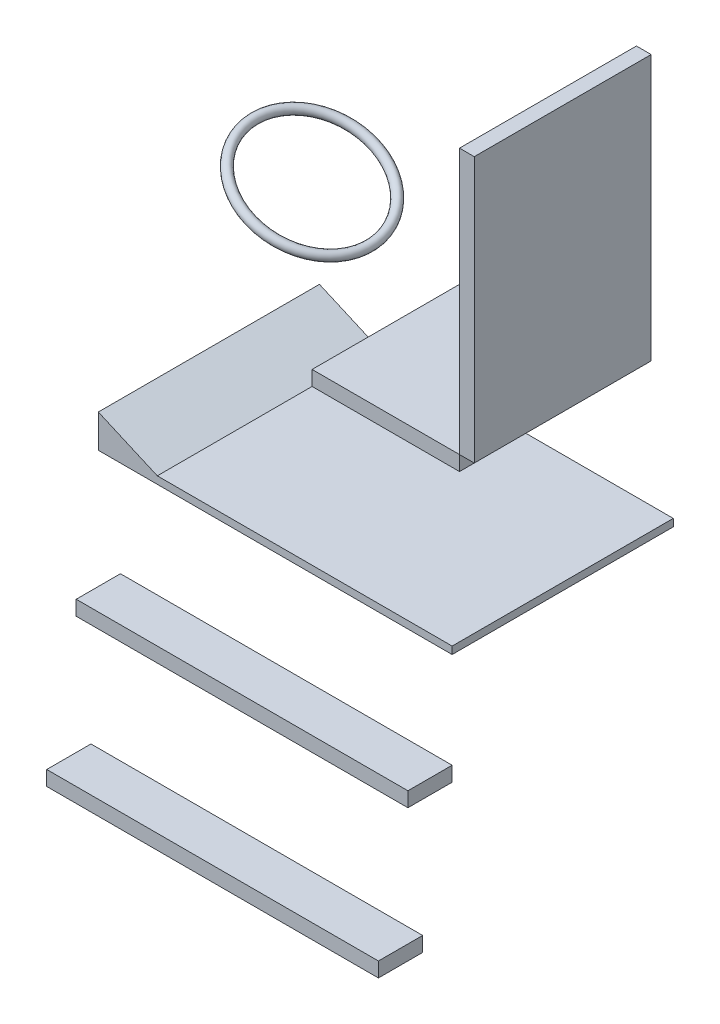
SolidWorks part; units mm, degrees
ref_plane "Right Plane" through (0, 0, 0) normal (0, 0, 1) x (1, 0, 0)
ref_plane "Ground Plane" through (0, 0, 0) normal (0, 1, 0) x (1, 0, 0)
ref_plane "Front Plane" through (0, 0, 0) normal (1, 0, 0) x (0, 0, -1)
ref_plane "Step 1 top 18in" through (0, 457.2, 0) normal (0, 1, 0) x (1, 0, 0)
ref_plane "Step 2 top 18in" through (0, 914.4, 0) normal (0, 1, 0) x (1, 0, 0)
ref_plane "Truck Floor 50in from ground" through (0, 1270, 0) normal (0, 1, 0) x (1, 0, 0)
ref_plane "Seat Bottom" through (0, 1778, 0) normal (0, 1, 0) x (1, 0, 0)
ref_plane "Steering Wheel Center Height" through (0, 2032, 0) normal (0, 1, 0) x (1, 0, 0)
ref_plane "Center Plane" through (0, 0, -381) normal (0, 0, 1) x (1, 0, 0)
sketch "Floor Dimensions" plane through (0, 1270, 0) normal (0, 1, 0) x (1, 0, 0)
  line L5 (0, 762) -> (0, 0)
  line L7 (0, 0) -> (1219.2, 0)
  line L8 (-670.56, 0) -> (670.56, 0) construction
  line L9 (1219.2, 0) -> (1219.2, 762)
  line L10 (1219.2, 762) -> (0, 762)
  point P3 (0, 381)
  dimension "D1" = 1219.2
  dimension "D2" = 762
sketch "Step 2" plane through (0, 914.4, 0) normal (0, 1, 0) x (1, 0, 0)
  line L0 (1219.2, 0) -> (1219.2, 762) construction
  line L1 (76.2, -152.4) -> (1219.2, -152.4)
  line L2 (76.2, -152.4) -> (76.2, 0)
  line L3 (76.2, 0) -> (1219.2, 0)
  line L4 (1219.2, -152.4) -> (1219.2, 0)
  line L5 (0, 0) -> (1219.2, 0) construction
  dimension "D1" = 1143
  dimension "D2" = 152.4
  dimension "D3" = 152.4
sketch "Sketch4" plane through (0, 457.2, 0) normal (0, 1, 0) x (1, 0, 0)
  line L0 (1219.2, -152.4) -> (1219.2, 0) construction
  line L1 (1219.2, -101.6) -> (76.2, -101.6)
  line L2 (1219.2, -101.6) -> (1219.2, -254)
  line L3 (1219.2, -254) -> (76.2, -254)
  line L4 (76.2, -101.6) -> (76.2, -254)
  line L5 (76.2, -152.4) -> (1219.2, -152.4) construction
  dimension "D1" = 152.4
  dimension "D2" = 101.6
extrude "Step-2" add sketch "Step 2" against normal blind 50.8
extrude "Step-1" add sketch "Sketch4" against normal blind 50.8 separate body
sketch "Sketch5" plane through (0, 1778, 0) normal (0, 1, 0) x (1, 0, 0)
  line L0 (660.4, 76.2) -> (660.4, 685.8)
  line L1 (660.4, 76.2) -> (1168.4, 76.2)
  line L2 (660.4, 685.8) -> (1168.4, 685.8)
  line L3 (1168.4, 76.2) -> (1168.4, 685.8)
  line L4 (660.4, 76.2) -> (1168.4, 685.8) construction
  line L5 (660.4, 685.8) -> (1168.4, 76.2) construction
  line L6 (-670.56, 381) -> (670.56, 381) construction
  line L7 (0, 762) -> (0, 0) construction
  point P1 (914.4, 381)
  dimension "D1" = 609.6
  dimension "D2" = 660.4
  dimension "D3" = 508
extrude "Seat-Bottom" add sketch "Sketch5" against normal blind 50.8 separate body
sketch "Sketch6" plane through (0, 0, -381) normal (0, 0, 1) x (1, 0, 0)
  line L0 (1219.2, 1778) -> (1219.2, 2692.4)
  line L7 (1168.4, 1778) -> (1168.4, 2692.4)
  line L8 (1219.2, 2692.4) -> (1168.4, 2692.4)
  line L9 (1168.4, 1778) -> (1219.2, 1778)
  line L10 (558.8, 1778) -> (-558.8, 1778) construction
  dimension "D1" = 914.4
  dimension "D2" = 1219.2
extrude "Seat-Back" add sketch "Sketch6" along normal up to vertex (-304.8 mm away) and the other way up to vertex (-304.8 mm away) separate body up to point (1168.4, 1778, -685.8) other way up to point (1168.4, 1778, -76.2)
sketch "Sketch7" plane through (0, 0, -381) normal (0, 0, 1) x (1, 0, 0)
  line L0 (0, 1358.9) -> (203.2, 1270)
  line L1 (0, -55) -> (0, 55) construction
  line L2 (0, 1270) -> (1219.2, 1270) construction
  line L3 (203.2, 1270) -> (1219.2, 1270)
  line L4 (1219.2, 1270) -> (0, 1270) construction
  line L5 (1219.2, 1270) -> (1219.2, 1244.6)
  line L6 (1219.2, 1244.6) -> (0, 1244.6)
  line L7 (0, 1244.6) -> (0, 1358.9)
  line L8 (660.4, 1727.2) -> (660.4, 1778) construction
  dimension "D1" = 25.4
  dimension "D2" = 457.2
  dimension "D3" = 88.9
extrude "Floor" add sketch "Sketch7" along normal up to vertex (381 mm away) and the other way up to vertex (381 mm away) separate body up to point (1219.2, 1270, 0) other way up to point (1219.2, 1270, -762)
sketch "Steering-tilt" plane through (0, 2032, 0) normal (0, 1, 0) x (1, 0, 0)
  line L0 (355.6, 762) -> (355.6, 0) construction
  line L1 (1219.2, 762) -> (0, 762) construction
  line L2 (0, 0) -> (1219.2, 0) construction
  line L3 (660.4, 685.8) -> (660.4, 76.2) construction
  dimension "D1" = 304.8
ref_plane "Steering Wheel Plane" through (841.8135, 1805.2749, 0) normal (-0.4226, -0.9063, 0) x (0, 0, 1)
sketch "Wheel Center" plane through (841.8135, 1805.2749, 0) normal (-0.4226, -0.9063, 0) x (0, 0, 1)
  circle A0 centre (-381, 536.7252) radius 217.4875
  dimension "D1" = 434.975
sketch "Sketch12" plane through (0, 0, -381) normal (0, 0, 1) x (1, 0, 0)
  line L0 (158.2647, 2124.019) -> (552.4859, 1940.1906) construction
  line L1 (461.9799, 1982.3942) -> (1221.6471, 1628.1556) construction
  circle A0 centre (158.2647, 2124.019) radius 15.875
  dimension "D1" = 31.75
sweep "Steering Wheel" add profiles "Sketch12" path "Wheel Center"
